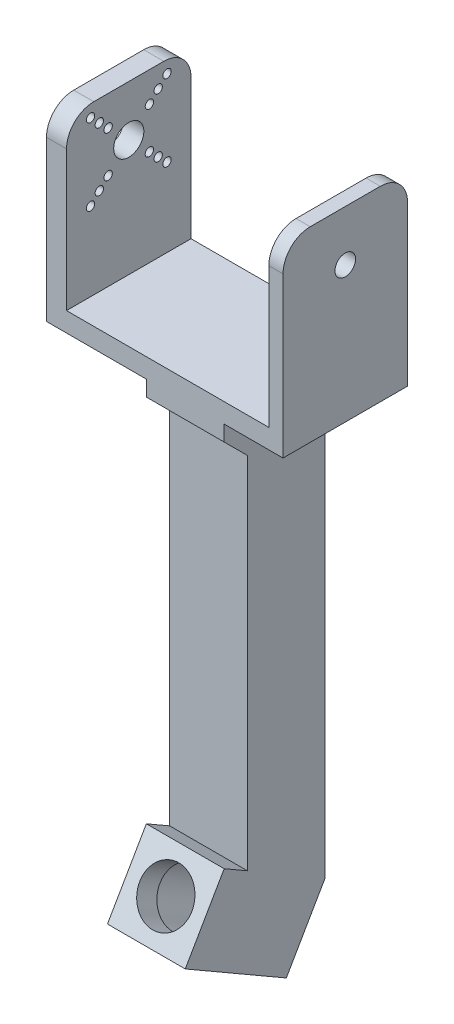
SolidWorks part; units mm, degrees
note: The reader was unsure of these and kept them because the rebuilt part matched: shared geometry of "Sketch1<3>".
ref_plane "Front Plane" through (0, 0, 0) normal (0, 0, 1) x (1, 0, 0)
ref_plane "Top Plane" through (0, 0, 0) normal (0, 1, 0) x (1, 0, 0)
ref_plane "Right Plane" through (0, 0, 0) normal (1, 0, 0) x (0, 0, -1)
sketch "Sketch1" plane through (0, 0, 0) normal (0, 1, 0) x (1, 0, 0)
  line L0 (-38.75, -38.75) -> (38.75, -38.75)
  line L1 (-38.75, -38.75) -> (-38.75, 38.75)
  line L2 (-38.75, 38.75) -> (38.75, 38.75)
  line L3 (38.75, -38.75) -> (38.75, 38.75)
  line L4 (-38.75, -38.75) -> (38.75, 38.75) construction
  line L5 (-38.75, 38.75) -> (38.75, -38.75) construction
  circle A0 centre (0, 0) radius 46.3155 construction
  circle A1 centre (32.75, 32.75) radius 1.83
  circle A2 centre (32.75, -32.75) radius 1.83
  circle A3 centre (-32.75, -32.75) radius 1.83
  circle A4 centre (-32.75, 32.75) radius 1.83
  circle A5 centre (0, 0) radius 13.5
  circle A6 centre (0, 0) radius 56.5 construction
  point P12 (0, 0)
  dimension "D2" = 3.66
  dimension "D4" = 27
  dimension "D5" = 113
  dimension "D1" = 65.5
  dimension "D3" = 6
extrude "Boss-Extrude1" add sketch "Sketch1" along normal blind 2.5
fillet "Fillet1" radius 3 4 edges at (38.75, 1.25, -38.75) (38.75, 1.25, 38.75) (-38.75, 1.25, -38.75) (-38.75, 1.25, 38.75)
sketch "Sketch2" plane through (0, 2.5, 0) normal (0, 1, 0) x (1, 0, 0)
  line L0 (0, 0) -> (20, 0) construction
  line L1 (-35.65, 16) -> (-30.5, 16)
  line L2 (-35.65, 16) -> (-35.65, -16)
  line L3 (-35.65, -16) -> (-30.5, -16)
  line L4 (-30.5, 16) -> (-30.5, -16)
  line L5 (20, 16) -> (25.15, 16) construction
  line L6 (20, 16) -> (20, -16) construction
  line L7 (20, -16) -> (25.15, -16) construction
  line L8 (25.15, 16) -> (25.15, -16)
  line L9 (21.5, -16) -> (21.5, 16)
  line L10 (21.5, 16) -> (25.15, 16)
  line L11 (21.5, -16) -> (25.15, -16)
  dimension "D1" = 50.5
  dimension "D2" = 20
  dimension "D3" = 5.15
  dimension "D4" = 32
  dimension "D5" = 1.5
extrude "Boss-Extrude2" add sketch "Sketch2" along normal blind 43
sketch "Sketch3" plane through (-35.65, 0, 0) normal (-1, 0, 0) x (0, 0, 1)
  line L0 (-5.3033, 37.8033) -> (0, 32.5) construction
  line L1 (16, 45.5) -> (16, 2.5) construction
  line L2 (16, 45.5) -> (16, 2.5) construction
  line L3 (-16, 45.5) -> (16, 45.5) construction
  circle A0 centre (0, 32.5) radius 3.875
  circle A1 centre (-5.3033, 37.8033) radius 1.075
  circle A15 centre (5.3033, 37.8033) radius 1.075
  circle A18 centre (5.3033, 27.1967) radius 1.075
  circle A21 centre (-5.3033, 27.1967) radius 1.075
  circle A24 centre (-7.566, 40.066) radius 1.075
  circle A25 centre (-9.8288, 42.3288) radius 1.075
  circle A26 centre (9.8288, 42.3288) radius 1.075
  circle A27 centre (7.566, 40.066) radius 1.075
  circle A28 centre (9.8288, 22.6712) radius 1.075
  circle A29 centre (7.566, 24.934) radius 1.075
  circle A30 centre (-9.8288, 22.6712) radius 1.075
  circle A31 centre (-7.566, 24.934) radius 1.075
  point P28 (0, 32.5)
  point P30 (0, 32.5)
  point P31 (0, 32.5)
  dimension "D1" = 7.75
  dimension "D2" = 2.15
  dimension "D3" = 3.2
  dimension "D4" = 7.5
  dimension "D6" = 3
  dimension "D8" = 13
  dimension "D5" = 4
  dimension "D7" = 4
extrude "Cut-Extrude1" cut sketch "Sketch3" against normal blind 10
sketch "Sketch4" plane through (25.15, 0, 0) normal (1, 0, 0) x (0, 0, -1)
  circle A0 centre (0, 32.5) radius 2.65
  circle A1 centre (0, 32.5) radius 3.875 construction
  circle A2 centre (0, 32.5) radius 3.875 construction
  dimension "D1" = 5.3
extrude "Cut-Extrude2" cut sketch "Sketch4" against normal blind 10
sketch "Sketch5" plane through (21.5, 0, 0) normal (-1, 0, 0) x (0, 0, 1)
  circle A0 centre (0, 32.5) radius 2.65 construction
  circle A1 centre (0, 32.5) radius 3.875 construction
  circle A2 centre (0, 32.5) radius 2.65
  circle A3 centre (0, 32.5) radius 3.875
extrude "Boss-Extrude3" add sketch "Sketch5" along normal blind 1.5
chamfer "Chamfer1" distance 1.5 angle 45 1 edges at (21.5, 32.5, -3.875)
extrude "Cut-Extrude4" cut sketch "Sketch1<3>" along normal up to surface (2.5 mm away) up to face at (-33.075, 2.5, 0)
sketch "Sketch1<3>" plane through (0, 0, 0) normal (0, 1, 0) x (1, 0, 0) same geometry as "Sketch1"
sketch "Sketch6" plane through (0, 2.5, 0) normal (0, -1, 0) x (1, 0, 0)
  line L1 (-35.65, 16) -> (25.15, 16)
  line L2 (-35.65, 16) -> (-35.65, -16)
  line L3 (-35.65, -16) -> (25.15, -16)
  line L4 (25.15, 16) -> (25.15, -16)
  line L5 (-15, -16) -> (15, -16)
  line L6 (-15, -16) -> (-15, 16)
  line L7 (-15, 16) -> (15, 16)
  line L8 (15, -16) -> (15, 16)
  line L9 (-15, -16) -> (15, 16) construction
  line L10 (-15, 16) -> (15, -16) construction
  point P6 (0, 0)
  dimension "D1" = 30
extrude "Boss-Extrude4" add sketch "Sketch6" along normal blind 5
sketch "Sketch7" plane through (0, -2.5, 0) normal (0, -1, 0) x (1, 0, 0)
  line L1 (-10, 10) -> (10, 10)
  line L2 (-10, 10) -> (-10, -10)
  line L3 (-10, -10) -> (10, -10)
  line L4 (10, 10) -> (10, -10)
  line L5 (-10, 10) -> (10, -10) construction
  line L6 (-10, -10) -> (10, 10) construction
  point P0 (0, 0)
  dimension "D1" = 20
extrude "Boss-Extrude5" add sketch "Sketch7" along normal blind 114
sketch "Sketch8" plane through (10, 0, 0) normal (-1, 0, 0) x (0, 0, 1)
  line L7 (-10, -116.5) -> (0, -133.8205)
  line L8 (-10, -116.5) -> (15.9808, -101.5)
  line L9 (0, -133.8205) -> (25.9808, -118.8205)
  line L10 (15.9808, -101.5) -> (25.9808, -118.8205)
  line L11 (-10, -116.5) -> (-10, -2.5) construction
  dimension "D1" = 60
  dimension "D2" = 20
  dimension "D3" = 30
extrude "Boss-Extrude7" add sketch "Sketch8" along normal up to surface (20 mm away) up to face at (-10, -59.5, 0)
sketch "Sketch10" plane through (0, -33.4551, -57.946) normal (0, -0.5, -0.866) x (-1, 0, 0)
  line L0 (-10, -95.892) -> (10, -115.892) construction
  line L1 (10, -115.892) -> (10, -95.892) construction
  circle A0 centre (0, -105.892) radius 8.25
  dimension "D1" = 16.5
extrude "Cut-Extrude6" cut sketch "Sketch10" against normal up to surface (30 mm away) up to face at (0, -110.1603, 20.9808)
sketch "Sketch11" plane through (0, -18.4551, -31.9652) normal (0, 0.5, 0.866) x (1, 0, 0)
  circle A0 centre (0, -105.892) radius 8.25 construction
  circle A1 centre (0, -105.892) radius 8.25
  circle A2 centre (0, -105.892) radius 6.7
  dimension "D1" = 13.4
extrude "Boss-Extrude8" add sketch "Sketch11" against normal blind 6
fillet "Fillet3" radius 7 4 edges at (-33.075, 45.5, -16) (-33.075, 45.5, 16) (23.325, 45.5, -16) (23.325, 45.5, 16)
chamfer "Chamfer2" distance 10 angle 45 2 edges at (0, -2.5, -10) (0, -2.5, 10)
